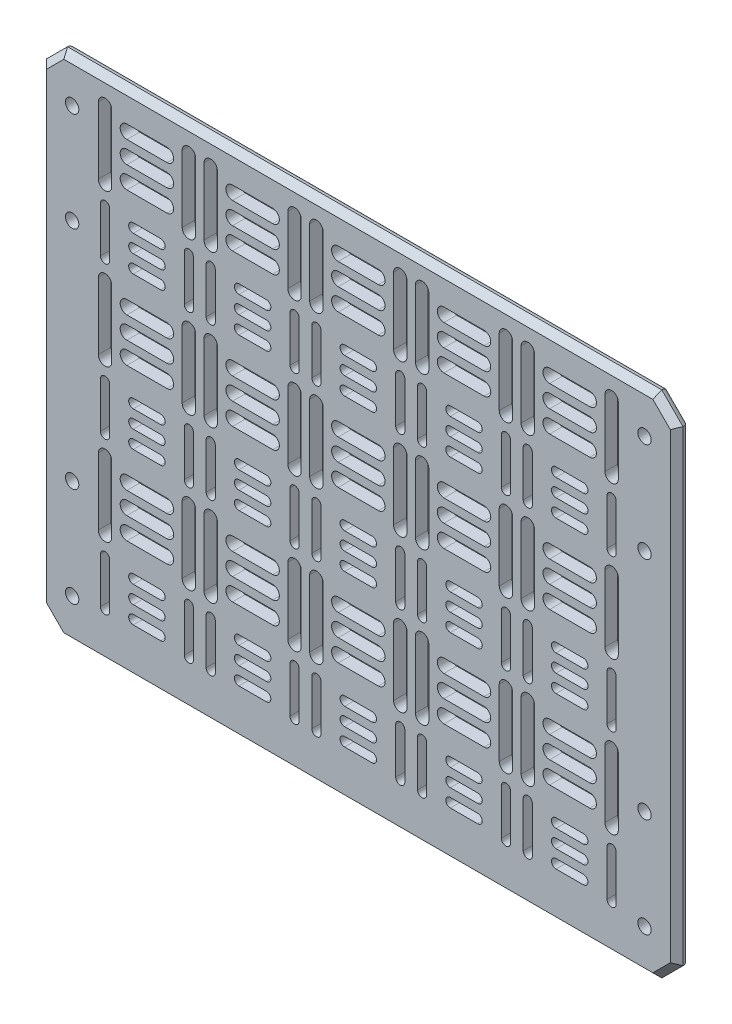
SolidWorks part; units mm, degrees
ref_plane "XY" through (0, 0, 0) normal (0, 0, 1) x (1, 0, 0)
ref_plane "-XZ" through (0, 0, 0) normal (0, 1, 0) x (1, 0, 0)
ref_plane "ZY" through (0, 0, 0) normal (1, 0, 0) x (0, 0, -1)
sketch "Esquisse1" plane through (0, 0, 0) normal (0, 0, 1) x (1, 0, 0)
  line L5 (-75, -60) -> (75, -60)
  line L6 (-75, -60) -> (-75, 60)
  line L7 (-75, 60) -> (75, 60)
  line L8 (75, -60) -> (75, 60)
  line L9 (-75, -60) -> (75, 60) construction
  line L10 (-75, 60) -> (75, -60) construction
  point P0 (0, 0)
  dimension "D1" = 120
  dimension "D2" = 150
extrude "Boss.-Extru.1" add sketch "Esquisse1" along normal blind 3
sketch "Esquisse2" plane through (0, 0, 0) normal (0, 0, 1) x (1, 0, 0)
  line L0 (0, -60) -> (0, 60) construction
  line L1 (-75, 0) -> (75, 0) construction
  line L2 (-9.875, 18.075) -> (-9.875, 2.325) construction
  line L3 (-9.875, -2.325) -> (-9.875, -13.075) construction
  line L4 (10.95, -2.325) -> (10.95, -13.075)
  line L5 (-11.45, 18.075) -> (-11.45, 2.325)
  line L6 (-8.3, 18.075) -> (-8.3, 2.325)
  line L7 (-10.95, -2.325) -> (-10.95, -13.075)
  line L8 (-8.8, -2.325) -> (-8.8, -13.075)
  line L9 (-4.725, 10.2) -> (4.725, 10.2) construction
  line L10 (-4.725, 11.775) -> (4.725, 11.775)
  line L11 (-4.725, 8.625) -> (4.725, 8.625)
  line L12 (-3.225, -7.7) -> (3.225, -7.7) construction
  line L13 (-3.225, -6.625) -> (3.225, -6.625)
  line L14 (-3.225, -8.775) -> (3.225, -8.775)
  line L15 (8.8, -2.325) -> (8.8, -13.075)
  line L16 (11.45, 18.075) -> (11.45, 2.325)
  line L17 (8.3, 18.075) -> (8.3, 2.325)
  line L26 (75, -60) -> (75, 60) construction
  line L27 (75, 60) -> (-75, 60) construction
  line L28 (-75, 60) -> (-75, -60) construction
  line L29 (-75, -60) -> (75, -60) construction
  line L30 (-4.725, 16.925) -> (4.725, 16.925)
  line L31 (-4.725, 13.775) -> (4.725, 13.775)
  line L32 (-4.725, 3.475) -> (4.725, 3.475)
  line L33 (-4.725, 6.625) -> (4.725, 6.625)
  line L34 (-3.225, -2.475) -> (3.225, -2.475)
  line L35 (-3.225, -4.625) -> (3.225, -4.625)
  line L36 (-3.225, -12.925) -> (3.225, -12.925)
  line L37 (-3.225, -10.775) -> (3.225, -10.775)
  circle A0 centre (-9.875, 18.075) radius 1.575 construction
  circle A1 centre (-9.875, 14.925) radius 1.575 construction
  circle A2 centre (-9.875, 11.775) radius 1.575 construction
  circle A3 centre (-9.875, 8.625) radius 1.575 construction
  circle A4 centre (-9.875, 5.475) radius 1.575 construction
  circle A5 centre (-9.875, 2.325) radius 1.575 construction
  circle A6 centre (-9.875, -2.325) radius 1.075 construction
  circle A7 centre (-9.875, -4.475) radius 1.075 construction
  circle A8 centre (-9.875, -6.625) radius 1.075 construction
  circle A9 centre (-9.875, -8.775) radius 1.075 construction
  circle A10 centre (-9.875, -10.925) radius 1.075 construction
  circle A11 centre (-9.875, -13.075) radius 1.075 construction
  arc A12 (-10.95, -2.325) -> (-8.8, -2.325) centre (-9.875, -2.325) cw
  arc A13 (-10.95, -13.075) -> (-8.8, -13.075) centre (-9.875, -13.075) ccw
  arc A14 (-11.45, 2.325) -> (-8.3, 2.325) centre (-9.875, 2.325) ccw
  arc A15 (-11.45, 18.075) -> (-8.3, 18.075) centre (-9.875, 18.075) cw
  circle A16 centre (-4.725, 10.2) radius 1.575 construction
  circle A17 centre (-1.575, 10.2) radius 1.575 construction
  circle A18 centre (1.575, 10.2) radius 1.575 construction
  circle A19 centre (4.725, 10.2) radius 1.575 construction
  arc A20 (4.725, 11.775) -> (4.725, 8.625) centre (4.725, 10.2) cw
  arc A21 (-4.725, 11.775) -> (-4.725, 8.625) centre (-4.725, 10.2) ccw
  circle A22 centre (-3.225, -7.7) radius 1.075 construction
  circle A23 centre (-1.075, -7.7) radius 1.075 construction
  circle A24 centre (1.075, -7.7) radius 1.075 construction
  circle A25 centre (3.225, -7.7) radius 1.075 construction
  arc A26 (3.225, -6.625) -> (3.225, -8.775) centre (3.225, -7.7) cw
  arc A27 (-3.225, -6.625) -> (-3.225, -8.775) centre (-3.225, -7.7) ccw
  arc A28 (10.95, -2.325) -> (8.8, -2.325) centre (9.875, -2.325) ccw
  arc A29 (10.95, -13.075) -> (8.8, -13.075) centre (9.875, -13.075) cw
  arc A30 (11.45, 2.325) -> (8.3, 2.325) centre (9.875, 2.325) cw
  arc A31 (11.45, 18.075) -> (8.3, 18.075) centre (9.875, 18.075) ccw
  arc A32 (4.725, 16.925) -> (4.725, 13.775) centre (4.725, 15.35) cw
  arc A33 (-4.725, 16.925) -> (-4.725, 13.775) centre (-4.725, 15.35) ccw
  arc A34 (4.725, 3.475) -> (4.725, 6.625) centre (4.725, 5.05) ccw
  arc A35 (-4.725, 3.475) -> (-4.725, 6.625) centre (-4.725, 5.05) cw
  arc A36 (3.225, -2.475) -> (3.225, -4.625) centre (3.225, -3.55) cw
  arc A37 (-3.225, -2.475) -> (-3.225, -4.625) centre (-3.225, -3.55) ccw
  arc A38 (3.225, -12.925) -> (3.225, -10.775) centre (3.225, -11.85) ccw
  arc A39 (-3.225, -12.925) -> (-3.225, -10.775) centre (-3.225, -11.85) cw
  point P69 (0, 10.2)
  point P70 (0, -7.7)
  point P71 (-9.875, -7.7)
  point P72 (-9.875, 10.2)
  point P76 (-9.875, -1.25)
  point P77 (-9.875, 0.75)
  point P78 (-6.3, 10.2)
  point P105 (-9.875, -14.15)
  point P106 (-9.875, 19.65)
  dimension "D1" = 3.15
  dimension "D2" = 2.15
  dimension "D3" = 2
  dimension "D4" = 2
  dimension "D7" = 22.9
  dimension "D8" = 33.8
  dimension "D6" = 2
  dimension "D10" = 2
  dimension "D5" = 2
  dimension "D9" = 2
extrude "Enlèv. mat.-Extru.1" cut sketch "Esquisse2" along normal up to next
pattern_linear "Répétition linéaire1" count 3 spacing 24.9 along (1, 0, 0) count 3 spacing 24.9 along (-1, 0, 0) of "Enlèv. mat.-Extru.1" pattern seed only yes
pattern_linear "Répétition linéaire2" count 2 spacing 35.8 along (0, 1, 0) count 2 spacing 35.8 along (0, -1, 0) of "Répétition linéaire1" pattern seed only yes
sketch "Esquisse3" plane through (0, 0, 0) normal (0, 0, 1) x (1, 0, 0)
  circle A0 centre (67.4227, -50) radius 1.575
  circle A2 centre (67.4227, -26.575) radius 1.575
  ellipse E3 centre (67.4227, -26.575) end of major axis (67.4227, -28.15) minor radius 1.569 construction
  ellipse E4 centre (67.4227, -50) end of major axis (67.4227, -51.575) minor radius 1.569 construction
  dimension "D1" = 3.15
extrude "Enlèv. mat.-Extru.2" cut sketch "Esquisse3" against normal through all both and the other way through all
mirror "Symétrie1" about plane through (0, 0, 0) normal (0, 1, 0) of "Enlèv. mat.-Extru.2"
mirror "Symétrie2" about plane through (0, 0, 0) normal (1, 0, 0) of "Symétrie1"
chamfer "Chanfrein1" distance 5 angle 45 4 edges at (75, -60, 1.5) (75, 60, 1.5) (-75, 60, 1.5) (-75, -60, 1.5)
chamfer "Chanfrein2" distance 1.5 angle 45 8 edges at (-72.5, -57.5, 3) (-75, 0, 3) (-72.5, 57.5, 3) (0, 60, 3) (72.5, 57.5, 3) (75, 0, 3) (72.5, -57.5, 3) (0, -60, 3)
fillet "Congé1" radius 1.5 7 edges at (-75, 0, 0) (-72.5, 57.5, 0) (0, 60, 0) (72.5, 57.5, 0) (75, 0, 0) (72.5, -57.5, 0) (0, -60, 0)
equation "\"D3@Répétition linéaire2\"=\"D8@Esquisse2\"+2"
equation "\"D3@Répétition linéaire1\"=\"D7@Esquisse2\"+2"
